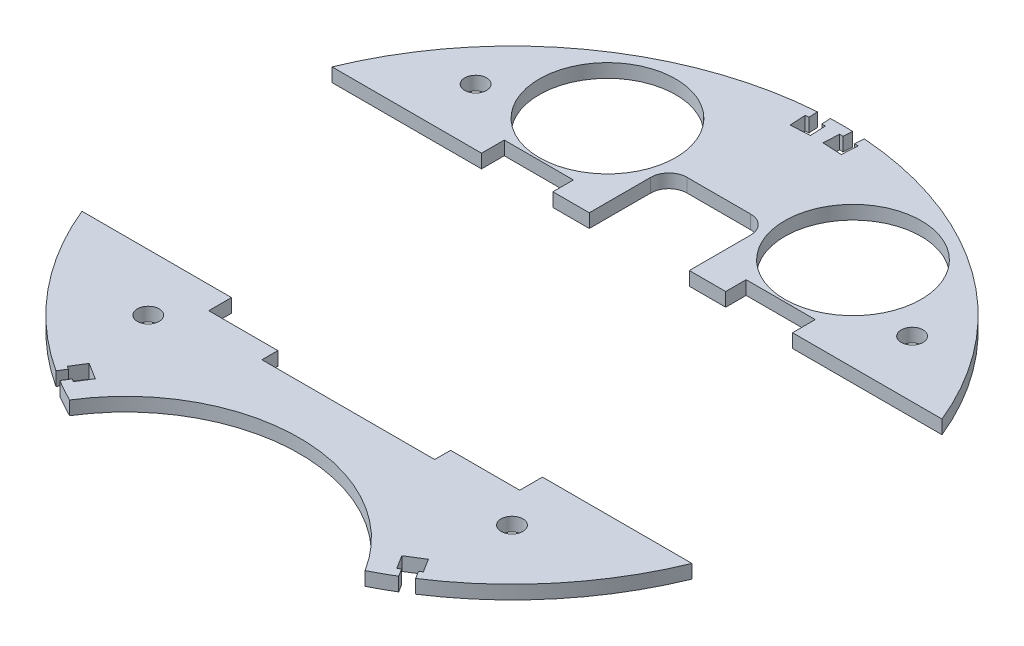
SolidWorks part; units mm, degrees
material "Acrylic (Medium-high impact)"
ref_plane "Front Plane" through (0, 0, 0) normal (0, 0, 1) x (1, 0, 0)
ref_plane "Top Plane" through (0, 0, 0) normal (0, 1, 0) x (1, 0, 0)
ref_plane "Right Plane" through (0, 0, 0) normal (1, 0, 0) x (0, 0, -1)
sketch "Sketch1" plane through (0, 0, 0) normal (0, 1, 0) x (1, 0, 0)
  line L0 (0, -85) -> (-32.4891, -64.8129) construction
  line L1 (0, -85) -> (0, 0) construction
  arc A0 (32.4891, -64.8129) -> (-32.4891, -64.8129) centre (0, 0) ccw
  arc A1 (32.4891, -64.8129) -> (-32.4891, -64.8129) centre (0, -85) ccw
  dimension "D1" = 145
  dimension "D2" = 76.5
  dimension "D3" = 85
extrude "Boss-Extrude1" add sketch "Sketch1" along normal blind 3
sketch "solenoid placement" plane through (0, 3, 0) normal (0, 1, 0) x (1, 0, 0)
  line L4 (-19, -36) -> (19, -36)
  line L5 (-19, -36) -> (19, -36)
  line L6 (19, -36) -> (19, 28)
  line L7 (19, -36) -> (19, 28)
  line L8 (19, 28) -> (-19, 28)
  line L9 (19, 28) -> (-19, 28)
  line L10 (-19, 28) -> (-19, -36)
  line L11 (-19, 28) -> (-19, -36)
  circle A1 centre (0, 0) radius 72.5 construction
  arc A2 (32.4891, -64.8129) -> (-32.4891, -64.8129) centre (0, 0) ccw construction
  dimension "D1" = 0
extrude "Cut-Extrude1" cut sketch "solenoid placement" against normal through all
sketch "Sketch3" plane through (0, 3, 0) normal (0, 1, 0) x (1, 0, 0)
  circle A1 centre (27, 48) radius 12
  circle A2 centre (-27, 48) radius 12
  dimension "D1" = 24
extrude "Cut-Extrude3" cut sketch "Sketch3" against normal through all
sketch "Sketch4" plane through (0, 3, 0) normal (0, 1, 0) x (1, 0, 0)
  circle A2 centre (40, -40) radius 2.4
  circle A3 centre (40, -40) radius 2.4
  circle A4 centre (-40, -40) radius 2.4
  circle A5 centre (-40, -40) radius 2.4
  circle A6 centre (48, 40) radius 2.4
  circle A7 centre (48, 40) radius 2.4
  circle A8 centre (-48, 40) radius 2.4
  circle A12 centre (-48, 40) radius 2.4
  dimension "D1" = 0
  dimension "D2" = 0
  dimension "D3" = 0
  dimension "D4" = 0
extrude "Cut-Extrude4" cut sketch "Sketch4" against normal through all
sketch "Sketch2" plane through (0, 3, 0) normal (0, 1, 0) x (1, 0, 0)
  line L0 (0, 0) -> (0, 72.5) construction
  line L1 (34.2, -27.5007) -> (34.2, -32.5007)
  line L2 (67.0818, -27.5007) -> (34.2, -27.5007)
  line L3 (34.2, 27.4993) -> (67.0823, 27.4993)
  line L4 (34.2, 32.4993) -> (34.2, 27.4993)
  line L5 (22.2, 32.4993) -> (34.2, 32.4993)
  line L6 (19, 32.4993) -> (22.2, 32.4993)
  line L7 (19, -32.5007) -> (19, 32.4993)
  line L8 (22.2, -32.5007) -> (19, -32.5007)
  line L9 (-34.2, -32.5007) -> (-22.2, -32.5007)
  line L10 (-22.2, -32.5007) -> (-19, -32.5007)
  line L11 (-19, -32.5007) -> (-19, 32.4993)
  line L12 (-19, 32.4993) -> (-22.2, 32.4993)
  line L13 (-22.2, 32.4993) -> (-34.2, 32.4993)
  line L14 (-34.2, 32.4993) -> (-34.2, 24.9993)
  line L15 (-34.2, 24.9993) -> (-68.0535, 24.9993)
  line L16 (-68.053, -25.0007) -> (-34.2, -25.0007)
  line L17 (-34.2, -25.0007) -> (-34.2, -32.5007)
  line L18 (-34.2, -32.5007) -> (-22.2, -32.5007)
  line L19 (-22.2, -32.5007) -> (-19, -32.5007)
  line L20 (-19, -32.5007) -> (-19, 32.4993)
  line L21 (-19, 32.4993) -> (-22.2, 32.4993)
  line L22 (-22.2, 32.4993) -> (-34.2, 32.4993)
  line L23 (-34.2, 32.4993) -> (-34.2, 27.4993)
  line L24 (-34.2, 27.4993) -> (-67.0823, 27.4993)
  line L25 (-67.0818, -27.5007) -> (-34.2, -27.5007)
  line L26 (-34.2, -27.5007) -> (-34.2, -32.5007)
  line L27 (34.2, -32.5007) -> (22.2, -32.5007)
  arc A0 (32.4891, -64.8129) -> (-32.4891, -64.8129) centre (0, 0) ccw construction
  arc A1 (67.0823, 27.4993) -> (67.0818, -27.5007) centre (0, 0) cw
  arc A2 (-68.0535, 24.9993) -> (-68.053, -25.0007) centre (0, 0) ccw
  arc A3 (-67.0823, 27.4993) -> (-67.0818, -27.5007) centre (0, 0) ccw
  dimension "D2" = 55
  dimension "D1" = 0
extrude "Cut-Extrude2" cut sketch "Sketch2" against normal through all
sketch "Sketch5" plane through (0, 3, 0) normal (0, 1, 0) x (1, 0, 0)
  line L8 (-11, 28) -> (11, 28)
  line L9 (11, 28) -> (11, 41.5)
  line L10 (7, 45.5) -> (-7, 45.5)
  line L11 (-11, 41.5) -> (-11, 28)
  line L12 (19, 28) -> (-19, 28) construction
  arc A4 (11, 41.5) -> (7, 45.5) centre (7, 41.5) ccw
  arc A5 (-7, 45.5) -> (-11, 41.5) centre (-7, 41.5) ccw
  point P10 (0, 28)
  point P13 (0, 28)
  line M18 (-19, 28) -> (19, 28)
  dimension "D3" = 4
  dimension "D1" = 22
  dimension "D2" = 17.5
extrude "Cut-Extrude5" cut sketch "Sketch5" against normal through all contours L10 A5 L11 L9 A4 M18 region at (0, 3, -36.6073)
sketch "Sketch6" plane through (0, 3, 0) normal (0, 1, 0) x (-1, 0, 0)
  circle A1 centre (-27, -48) radius 15
  circle A2 centre (-27, -48) radius 15
  circle A3 centre (27, -48) radius 15
  circle A4 centre (27, -48) radius 15
  dimension "D1" = 0
  dimension "D2" = 0
extrude "Cut-Extrude10" cut sketch "Sketch6" against normal through all
sketch "Sketch7" plane through (0, 3, 0) normal (0, 1, 0) x (1, 0, 0)
  line L8 (-5.0378, 70.3327) -> (-5.8118, 70.2922)
  line L9 (-5.8118, 70.2922) -> (-5.6286, 66.797)
  line L10 (-5.6286, 66.797) -> (-1.3844, 67.0194)
  line L11 (-1.3844, 67.0194) -> (-1.5676, 70.5146)
  line L12 (-1.5676, 70.5146) -> (-2.3415, 70.474)
  line L13 (-2.3415, 70.474) -> (-2.4462, 72.4713)
  line L14 (-2.4462, 72.4713) -> (-5.1425, 72.33)
  line L15 (-5.1425, 72.33) -> (-5.0378, 70.3327)
  line L16 (-5.0378, 70.3327) -> (-5.8118, 70.2922)
  line L17 (-5.8118, 70.2922) -> (-5.6286, 66.797)
  line L18 (-5.6286, 66.797) -> (-1.3844, 67.0194)
  line L19 (-1.3844, 67.0194) -> (-1.5676, 70.5146)
  line L20 (-1.5676, 70.5146) -> (-2.3415, 70.474)
  line L21 (-2.3415, 70.474) -> (-2.4462, 72.4713)
  line L22 (-2.4462, 72.4713) -> (-5.1425, 72.33)
  line L23 (-5.1425, 72.33) -> (-5.0378, 70.3327)
  line L24 (5.8118, 70.2922) -> (5.0378, 70.3327)
  line L25 (5.6286, 66.797) -> (5.8118, 70.2922)
  line L26 (1.3844, 67.0194) -> (5.6286, 66.797)
  line L27 (1.5676, 70.5146) -> (1.3844, 67.0194)
  line L28 (2.3415, 70.474) -> (1.5676, 70.5146)
  line L29 (2.4462, 72.4713) -> (2.3415, 70.474)
  line L30 (5.1425, 72.33) -> (2.4462, 72.4713)
  line L31 (5.0378, 70.3327) -> (5.1425, 72.33)
  line L32 (5.8118, 70.2922) -> (5.0378, 70.3327)
  line L33 (5.6286, 66.797) -> (5.8118, 70.2922)
  line L34 (1.3844, 67.0194) -> (5.6286, 66.797)
  line L35 (1.5676, 70.5146) -> (1.3844, 67.0194)
  line L36 (2.3415, 70.474) -> (1.5676, 70.5146)
  line L37 (2.4462, 72.4713) -> (2.3415, 70.474)
  line L38 (5.1425, 72.33) -> (2.4462, 72.4713)
  line L39 (5.0378, 70.3327) -> (5.1425, 72.33)
  line L40 (38.5042, -59.072) -> (39.1614, -58.6613)
  line L41 (39.564, -60.7681) -> (38.5042, -59.072)
  line L42 (37.2743, -62.1989) -> (39.564, -60.7681)
  line L43 (36.2144, -60.5028) -> (37.2743, -62.1989)
  line L44 (35.5572, -60.9135) -> (36.2144, -60.5028)
  line L45 (33.7025, -57.9453) -> (35.5572, -60.9135)
  line L46 (37.3067, -55.6931) -> (33.7025, -57.9453)
  line L47 (39.1614, -58.6613) -> (37.3067, -55.6931)
  line L48 (38.5042, -59.072) -> (39.1614, -58.6613)
  line L49 (39.564, -60.7681) -> (38.5042, -59.072)
  line L50 (37.2743, -62.1989) -> (39.564, -60.7681)
  line L51 (36.2144, -60.5028) -> (37.2743, -62.1989)
  line L52 (35.5572, -60.9135) -> (36.2144, -60.5028)
  line L53 (33.7025, -57.9453) -> (35.5572, -60.9135)
  line L54 (37.3067, -55.6931) -> (33.7025, -57.9453)
  line L55 (39.1614, -58.6613) -> (37.3067, -55.6931)
  line L56 (-39.1614, -58.6613) -> (-38.5042, -59.072)
  line L57 (-37.3067, -55.6931) -> (-39.1614, -58.6613)
  line L58 (-33.7025, -57.9453) -> (-37.3067, -55.6931)
  line L59 (-35.5572, -60.9135) -> (-33.7025, -57.9453)
  line L60 (-36.2144, -60.5028) -> (-35.5572, -60.9135)
  line L61 (-37.2743, -62.1989) -> (-36.2144, -60.5028)
  line L62 (-39.564, -60.7681) -> (-37.2743, -62.1989)
  line L63 (-38.5042, -59.072) -> (-39.564, -60.7681)
  line L64 (-39.1614, -58.6613) -> (-38.5042, -59.072)
  line L65 (-37.3067, -55.6931) -> (-39.1614, -58.6613)
  line L66 (-33.7025, -57.9453) -> (-37.3067, -55.6931)
  line L67 (-35.5572, -60.9135) -> (-33.7025, -57.9453)
  line L68 (-36.2144, -60.5028) -> (-35.5572, -60.9135)
  line L69 (-37.2743, -62.1989) -> (-36.2144, -60.5028)
  line L70 (-39.564, -60.7681) -> (-37.2743, -62.1989)
  line L71 (-38.5042, -59.072) -> (-39.564, -60.7681)
  dimension "D1" = 0
  dimension "D2" = 0
  dimension "D3" = 0
  dimension "D4" = 0
extrude "Cut-Extrude11" cut sketch "Sketch7" against normal through all
sketch "Sketch8" plane through (0, 3, 0) normal (0, 1, 0) x (1, 0, 0)
  line L2 (7, 48.5) -> (-7, 48.5)
  line L3 (7.1569, 48.5) -> (-7.1569, 48.5)
  line L8 (-8.4675, 63.6441) -> (-1.2274, 64.0235)
  line L9 (-8.8077, 70.1352) -> (-8.4675, 63.6441)
  line L10 (-6.4702, 63.7487) -> (-0.1047, 64.0823)
  line L11 (-8.6309, 66.7627) -> (-8.5721, 65.6413)
  line L15 (8.4675, 63.6441) -> (8.8077, 70.1352)
  line L16 (1.2274, 64.0235) -> (8.4675, 63.6441)
  line L17 (8.5721, 65.6413) -> (8.6309, 66.7627)
  line L18 (0.1047, 64.0823) -> (6.4702, 63.7487)
  circle A2 centre (-27, 48) radius 18
  arc A3 (-9.1412, 50.25) -> (-18.004, 63.5907) centre (-27, 48) ccw
  circle A5 centre (27, 48) radius 18
  arc A6 (18.004, 63.5907) -> (9.1412, 50.25) centre (27, 48) ccw
  arc A8 (-4.9291, 69.325) -> (-64.3065, 26.3614) centre (0, 0) ccw
  arc A9 (-10.9431, 68.6331) -> (-17.5082, 67.2585) centre (0, 0) ccw
  arc A10 (17.5082, 67.2585) -> (10.9431, 68.6331) centre (0, 0) ccw
  arc A11 (-9.1412, 50.25) -> (-7.1569, 48.5) centre (-7.1569, 50.5) ccw
  arc A12 (9.1412, 50.25) -> (7.1569, 48.5) centre (7.1569, 50.5) cw
  arc A13 (17.5082, 67.2585) -> (18.004, 63.5907) centre (17.0044, 65.323) cw
  arc A14 (10.9431, 68.6331) -> (8.6309, 66.7627) centre (10.6282, 66.658) ccw
  arc A15 (8.5721, 65.6413) -> (6.4702, 63.7487) centre (6.5749, 65.746) cw
  arc A16 (-0.1047, 64.0823) -> (0.1047, 64.0823) centre (0, 62.0851) cw
  arc A17 (-6.4702, 63.7487) -> (-8.5721, 65.6413) centre (-6.5749, 65.746) cw
  arc A18 (-8.6309, 66.7627) -> (-10.9431, 68.6331) centre (-10.6282, 66.658) ccw
  arc A19 (-18.004, 63.5907) -> (-17.5082, 67.2585) centre (-17.0044, 65.323) cw
  dimension "D5" = 2
  dimension "D1" = 3
  dimension "D2" = 3
  dimension "D3" = 3
  dimension "D4" = 3
  dimension "D6" = 3
  dimension "D7" = 3
extrude "Cut-Extrude12" [suppressed] cut sketch "Sketch8" against normal through all and the other way through all
equation "\"smallPulleyTeeth\"= 30"
equation "\"largePulleyTeeth\"= 30"
equation "\"eighthThick\"= 3.0mm"
equation "\"sixteenthThick\" = 1.7mm"
equation "\"quarterThick\"=6.0mm"
equation "\"OD\" = 145mm"
equation "\"puckAngle\" = 60.5deg"
equation "\"D1@Sketch1\"=\"OD\""
equation "\"puckDiam\" = 76.5mm"
equation "\"D2@Sketch1\"=\"puckDiam\""
equation "\"D1@Boss-Extrude1\"=\"eighthThick\""
equation "\"axlePress\" = 5.9mm"
equation "\"press\" = 0.2mm"
equation "\"wheelClear\" = 0.3mm"
equation "\"10-32clear\" = 4.8mm"
equation "\"6-32clear\" = 3.3mm"
equation "\"8-32clear\" = 4.0mm"
equation "\"wheelHeight\" = 22mm"
equation "\"wheelWell\" = 65mm"
equation "\"puckDist\" = 85mm"
equation "\"scoopFillet\" = 5mm"
equation "\"4-40clear\" = 3.0mm"
equation "\"D3@Sketch1\"=\"puckDist\""
